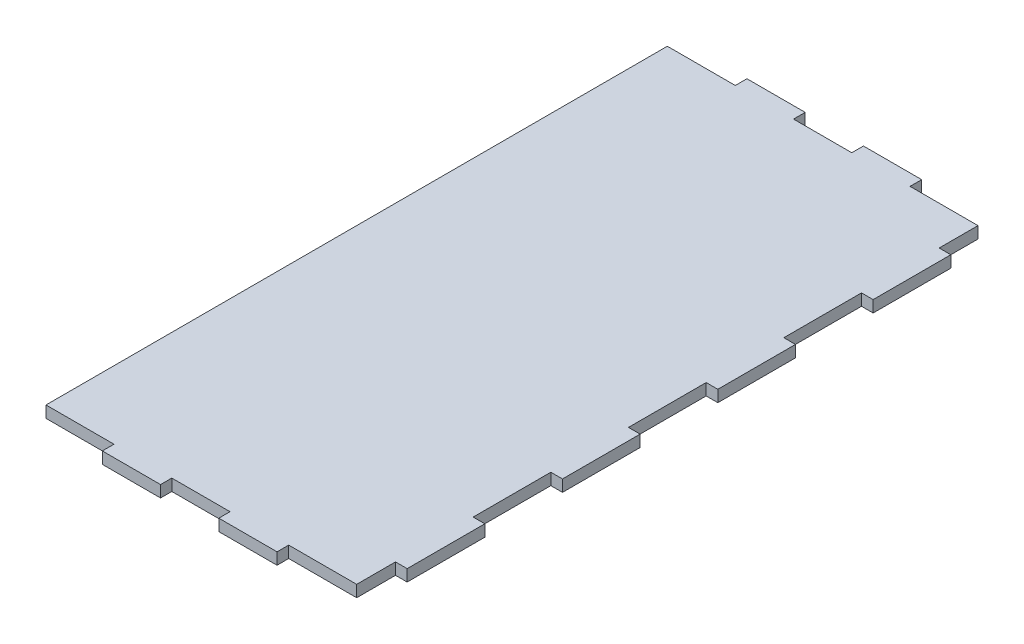
SolidWorks part; units mm, degrees
ref_plane "Alzado" through (0, 0, 0) normal (0, 0, 1) x (1, 0, 0)
ref_plane "Planta" through (0, 0, 0) normal (0, 1, 0) x (1, 0, 0)
ref_plane "Vista lateral" through (0, 0, 0) normal (1, 0, 0) x (0, 0, -1)
sketch "Croquis1" plane through (0, 0, 0) normal (0, 1, 0) x (1, 0, 0)
  line L0 (23, 3) -> (38, 3)
  line L1 (88.5, 16) -> (88.5, 36)
  line L2 (85.5, 166) -> (68, 166)
  line L4 (5.5, 153) -> (5.5, 13)
  line L5 (5.5, 73) -> (5.5, 93)
  line L6 (5.5, 166) -> (23, 166)
  line L7 (23, 166) -> (23, 169)
  line L8 (23, 169) -> (38, 169)
  line L9 (5.5, 113) -> (5.5, 133)
  line L10 (38, 169) -> (38, 166)
  line L11 (38, 166) -> (45.5, 166)
  line L12 (23, 166) -> (5.5, 166)
  line L13 (53, 169) -> (53, 166)
  line L14 (68, 169) -> (53, 169)
  line L15 (5.5, 53) -> (5.5, 33)
  line L16 (68, 166) -> (68, 169)
  line L17 (53, 166) -> (38, 166)
  line L18 (5.5, 153) -> (5.5, 166)
  line L19 (5.5, 13) -> (5.5, 6)
  line L20 (85.5, 156) -> (85.5, 153.3969)
  line L21 (53, 5.8969) -> (38, 5.8969)
  line L22 (38, 5.8969) -> (38, 3)
  line L23 (38, 3) -> (23, 3)
  line L24 (23, 3) -> (23, 6)
  line L25 (23, 6) -> (5.5, 6)
  line L26 (68, 6) -> (85.5, 6)
  line L27 (68, 3) -> (68, 6)
  line L28 (53, 5.8969) -> (53, 3)
  line L29 (85.5, 16) -> (85.5, 6)
  line L30 (85.5, 156) -> (85.5, 166)
  line L31 (85.5, 76) -> (88.5, 76)
  line L32 (88.5, 56) -> (85.5, 56)
  line L33 (85.5, 56) -> (85.5, 36)
  line L34 (85.5, 36) -> (88.5, 36)
  line L35 (88.5, 16) -> (85.5, 16)
  line L36 (88.5, 156) -> (85.5, 156)
  line L37 (85.5, 136) -> (88.5, 136)
  line L38 (85.5, 116) -> (85.5, 136)
  line L39 (88.5, 116) -> (85.5, 116)
  line L40 (85.5, 96) -> (88.5, 96)
  line L41 (85.5, 76) -> (85.5, 96)
  line L42 (88.5, 136) -> (88.5, 156)
  line L43 (53, 3) -> (68, 3)
  line L44 (88.5, 56) -> (88.5, 76)
  line L45 (88.5, 96) -> (88.5, 116)
  dimension "D2" = 80
  dimension "D3" = 80
  dimension "D5" = 3
  dimension "D6" = 20
  dimension "D7" = 3
  dimension "D9" = 3
  dimension "D10" = 15
  dimension "D11" = 17.5
  dimension "D12" = 160
  dimension "D13" = 15
  dimension "D14" = 10
  dimension "D15" = 10
extrude "Saliente-Extruir1" add sketch "Croquis1" along normal blind 3 contours L15 L19 L25 L24 L0 L22 L21 L28 L43 L27 L26 L29 L35 L1 L34 L33 L32 L44 L31 L41 L40 L45 L39 L38 L37 L42 L36 L30 L2 L18 L9 L5 region at (46.2533, 0, -85.9906)
